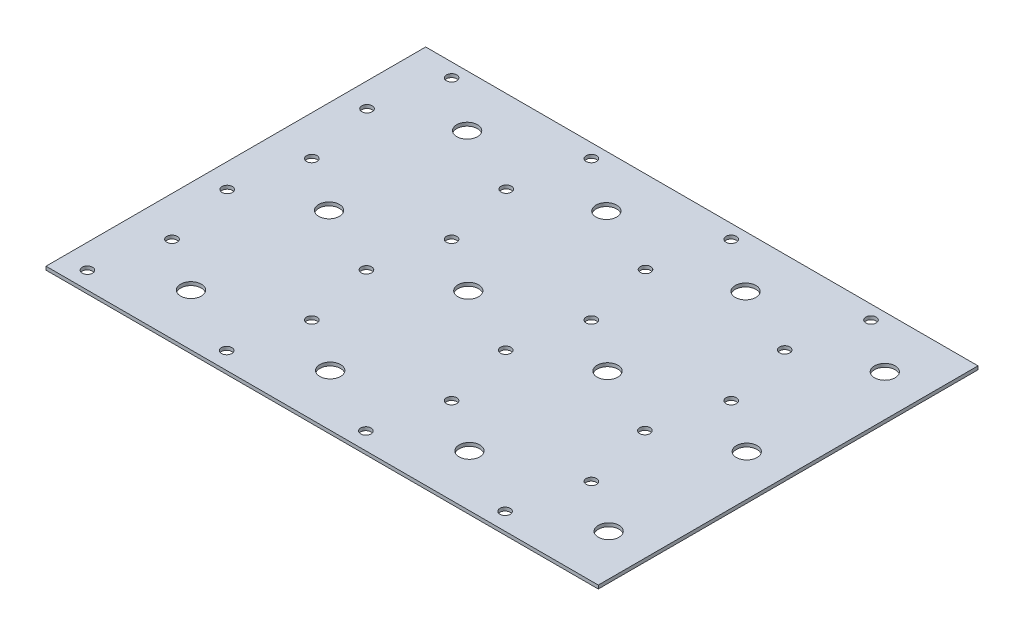
SolidWorks part; units mm, degrees
note: '?' marks a value the reader was unsure of.
ref_plane "Front Plane" through (0, 0, 0) normal (0, 0, 1) x (1, 0, 0)
ref_plane "Top Plane" through (0, 0, 0) normal (0, 1, 0) x (1, 0, 0)
ref_plane "Right Plane" through (0, 0, 0) normal (1, 0, 0) x (0, 0, -1)
sketch "Sketch1" plane through (0, 0, 0) normal (0, 1, 0) x (1, 0, 0)
  line L1 (-80, -55) -> (80, -55)
  line L2 (-80, -55) -> (-80, 55)
  line L3 (-80, 55) -> (80, 55)
  line L4 (80, -55) -> (80, 55)
  line L5 (-80, -55) -> (80, 55) construction
  line L6 (-80, 55) -> (80, -55) construction
  point P0 (0, 0)
  dimension "D1" = 160
  dimension "D2" = 110
extrude "Boss-Extrude1" add sketch "Sketch1" along normal blind 1
sketch "Sketch2" plane through (0, 1, 0) normal (0, 1, 0) x (1, 0, 0)
  line L0 (-80, 55) -> (-80, -55) construction
  line L1 (80, 55) -> (-80, 55) construction
  line L2 (80, -55) -> (80, 55) construction
  line L3 (-80, -55) -> (80, -55) construction
  circle A0 centre (-53, 40) radius 3
  circle A1 centre (-12.6667, 40) radius 3
  circle A2 centre (27.6667, 40) radius 3
  circle A3 centre (68, 40) radius 3
  circle A4 centre (-12.6667, 0) radius 3
  circle A5 centre (27.6667, 0) radius 3
  circle A6 centre (68, 0) radius 3
  circle A7 centre (-12.6667, -40) radius 3
  circle A8 centre (27.6667, -40) radius 3
  circle A9 centre (68, -40) radius 3
  circle A10 centre (-53, 0) radius 3
  circle A11 centre (-53, -40) radius 3
  circle A12 centre (-68.5, 51) radius 1.5
  circle A13 centre (-28, 51) radius 1.5
  circle A14 centre (12.5, 51) radius 1.5
  circle A15 centre (53, 51) radius 1.5
  circle A16 centre (-28, 10.5) radius 1.5
  circle A17 centre (12.5, 10.5) radius 1.5
  circle A18 centre (53, 10.5) radius 1.5
  circle A19 centre (-28, -30) radius 1.5
  circle A20 centre (12.5, -30) radius 1.5
  circle A21 centre (53, -30) radius 1.5
  circle A22 centre (-68.5, 10.5) radius 1.5
  circle A23 centre (-68.5, -30) radius 1.5
  circle A24 centre (-73, 31) radius 1.5
  circle A25 centre (-32.6667, 31) radius 1.5
  circle A26 centre (7.6667, 31) radius 1.5
  circle A27 centre (48, 31) radius 1.5
  circle A28 centre (-32.6667, -9.5) radius 1.5
  circle A29 centre (7.6667, -9.5) radius 1.5
  circle A30 centre (48, -9.5) radius 1.5
  circle A31 centre (-32.6667, -50) radius 1.5
  circle A32 centre (7.6667, -50) radius 1.5
  circle A33 centre (48, -50) radius 1.5
  circle A34 centre (-73, -9.5) radius 1.5
  circle A35 centre (-73, -50) radius 1.5
  dimension "D1" = 6
  dimension "D8" = 3
  dimension "D15" = 3
  dimension "D2" = 27
  dimension "D3" = 15
  dimension "D6" = 12
  dimension "D7" = 15
  dimension "D9" = 11.5
  dimension "D12" = 27
  dimension "D13" = 4
  dimension "D14" = 25
  dimension "D16" = 24
  dimension "D17" = 7
  dimension "D20" = 32
  dimension "D21" = 5
  dimension "D4" = 4
  dimension "D5" = 3
  dimension "D10" = 4
  dimension "D11" = 3
  dimension "D18" = 4
  dimension "D19" = 3
extrude "Cut-Extrude1" cut sketch "Sketch2" against normal up to next (1 mm away)
ref_axis "Axis1" through (-12.6667, 0, 0) along (0, 1, 0)?
ref_axis "Axis2" through (-53, 0, -40) along (0, 1, 0)?
ref_axis "Axis3" through (-53, 0, 40) along (0, 1, 0)?
ref_plane "Plane1" through (-6.2808, 0, -6.3331) normal (-0.7042, 0, -0.71) x (-0.71, 0, 0.7042)
ref_plane "Plane2" through (-6.2808, 0, 6.3331) normal (-0.7042, 0, 0.71) x (0.71, 0, 0.7042)
